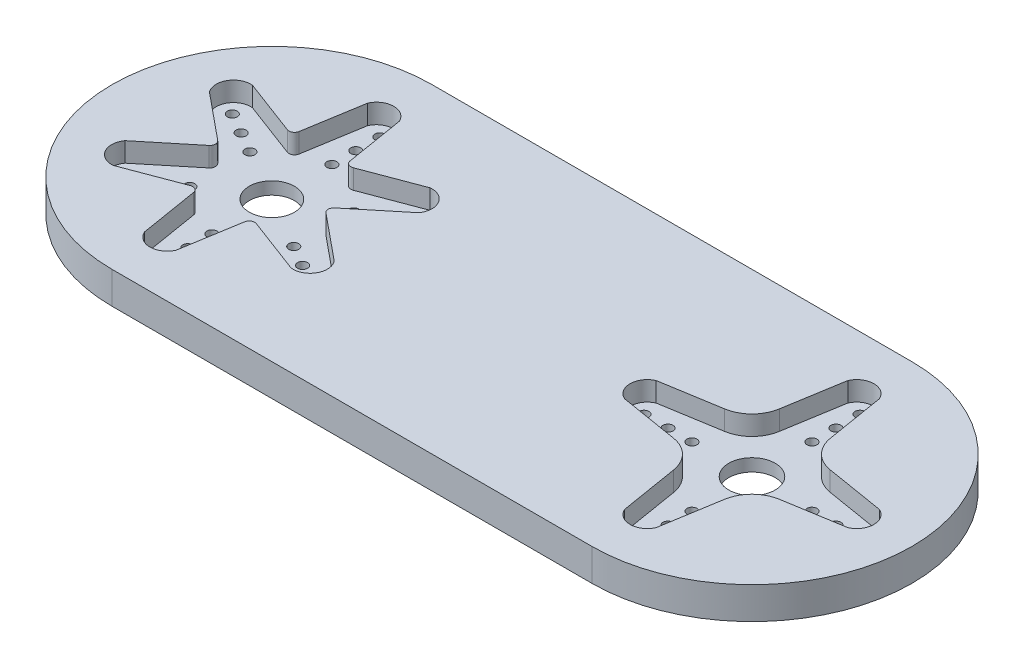
SolidWorks part; units mm, degrees
material "PLA"
ref_plane "Front Plane" through (0, 0, 0) normal (0, 0, 1) x (1, 0, 0)
ref_plane "Top Plane" through (0, 0, 0) normal (0, 1, 0) x (1, 0, 0)
ref_plane "Right Plane" through (0, 0, 0) normal (1, 0, 0) x (0, 0, -1)
sketch "Sketch1" plane through (0, 0, 0) normal (0, 1, 0) x (1, 0, 0)
  line L0 (-30, 0) -> (30, 0) construction
  line L1 (-30, 20) -> (30, 20)
  line L2 (-30, -20) -> (30, -20)
  arc A0 (-30, 20) -> (-30, -20) centre (-30, 0) ccw
  arc A1 (30, -20) -> (30, 20) centre (30, 0) ccw
  point P2 (0, 0)
  dimension "D1" = 60
  dimension "D2" = 40
extrude "Boss-Extrude1" add sketch "Sketch1" along normal blind 4
sketch "Sketch2" plane through (0, 4, 0) normal (0, 1, 0) x (1, 0, 0)
  line L0 (-30.0441, 0.0218) -> (-30.0441, -7.4787) construction
  line L1 (-30.0441, 0.0218) -> (-26.8597, 6.6199) construction
  line L2 (-30.0441, 0.0218) -> (-25.9221, 6.0786) construction
  line L3 (-30.0441, 0.0218) -> (-30.0441, 15.2618) construction
  line L4 (-30.0441, -7.4787) -> (-30.0441, -10.4787) construction
  line L5 (-30.0441, -10.4787) -> (-30.0441, -13.4787) construction
  line L18 (-30, 20) -> (-30, -20) construction
  line L19 (30, 20) -> (-30, 20) construction
  line L20 (-26.8597, 6.6199) -> (-28.0706, 13.9723)
  line L21 (-33.2284, 6.6199) -> (-32.0175, 13.9723)
  line L22 (-25.9221, 6.0786) -> (-18.9493, 8.706)
  line L23 (-22.7377, 0.5631) -> (-16.9759, 5.288)
  line L24 (-22.7377, -0.5195) -> (-16.9759, -5.2445)
  line L25 (-25.9221, -6.035) -> (-18.9493, -8.6625)
  line L26 (-26.8597, -6.5763) -> (-28.0706, -13.9287)
  line L27 (-33.2284, -6.5763) -> (-32.0175, -13.9287)
  line L28 (-34.166, -6.035) -> (-41.1388, -8.6625)
  line L29 (-37.3504, -0.5195) -> (-43.1122, -5.2445)
  line L30 (-37.3504, 0.5631) -> (-43.1122, 5.288)
  line L31 (-34.166, 6.0786) -> (-41.1388, 8.706)
  line L32 (30, 20) -> (30, -20) construction
  line L33 (30, 0) -> (30, -7.5005) construction
  line L34 (36.5981, -3.1844) -> (43.9505, -1.9734)
  line L35 (36.5981, 3.1844) -> (43.9505, 1.9734)
  line L36 (30, 0) -> (33.1844, 6.5981) construction
  line L37 (30, 0) -> (34.1219, 6.0568) construction
  line L38 (30, 0) -> (30, 15.24) construction
  line L39 (30, -7.5005) -> (30, -10.5005) construction
  line L40 (30, -10.5005) -> (30, -13.5005) construction
  line L41 (26.8156, -6.5981) -> (28.0266, -13.9505)
  line L42 (33.1844, -6.5981) -> (31.9734, -13.9505)
  line L43 (23.4019, 3.1844) -> (16.0495, 1.9734)
  line L44 (23.4019, -3.1844) -> (16.0495, -1.9734)
  line L45 (33.1844, 6.5981) -> (31.9734, 13.9505)
  line L46 (26.8156, 6.5981) -> (28.0266, 13.9505)
  line L47 (33.1844, -6.5981) -> (31.9734, -13.9505)
  line L48 (26.8156, -6.5981) -> (28.0266, -13.9505)
  arc A29 (-30, 20) -> (-30, -20) centre (-30, 0) ccw construction
  arc A30 (-32.0175, 13.9723) -> (-28.0706, 13.9723) centre (-30.0441, 13.107) cw
  arc A31 (-18.9493, 8.706) -> (-16.9759, 5.288) centre (-18.7119, 6.5644) cw
  arc A32 (-16.9759, -5.2445) -> (-18.9493, -8.6625) centre (-18.7119, -6.5208) cw
  arc A33 (-28.0706, -13.9287) -> (-32.0175, -13.9287) centre (-30.0441, -13.0635) cw
  arc A34 (-41.1388, -8.6625) -> (-43.1122, -5.2445) centre (-41.3762, -6.5208) cw
  arc A35 (-43.1122, 5.288) -> (-41.1388, 8.706) centre (-41.3762, 6.5644) cw
  arc A36 (-26.8597, 6.6199) -> (-25.9221, 6.0786) centre (-26.169, 6.7336) ccw
  arc A37 (-22.7377, 0.5631) -> (-22.7377, -0.5195) centre (-22.2939, 0.0218) ccw
  arc A38 (-25.9221, -6.035) -> (-26.8597, -6.5763) centre (-26.169, -6.6901) ccw
  arc A39 (-33.2284, -6.5763) -> (-34.166, -6.035) centre (-33.9191, -6.6901) ccw
  arc A40 (-37.3504, -0.5195) -> (-37.3504, 0.5631) centre (-37.7942, 0.0218) ccw
  arc A41 (-34.166, 6.0786) -> (-33.2284, 6.6199) centre (-33.9191, 6.7336) ccw
  circle A42 centre (-30.0441, -7.4787) radius 0.625
  circle A43 centre (-30.0441, -10.4787) radius 0.625
  circle A44 centre (-41.7358, -6.7285) radius 0.625
  circle A45 centre (-39.1377, -5.2285) radius 0.625
  circle A46 centre (-36.5396, -3.7285) radius 0.625
  circle A47 centre (-41.7358, 6.772) radius 0.625
  circle A48 centre (-39.1377, 5.272) radius 0.625
  circle A49 centre (-36.5396, 3.772) radius 0.625
  circle A50 centre (-30.0441, 13.5222) radius 0.625
  circle A51 centre (-30.0441, 10.5222) radius 0.625
  circle A52 centre (-30.0441, 7.5222) radius 0.625
  circle A53 centre (-18.3523, 6.772) radius 0.625
  circle A54 centre (-20.9504, 5.272) radius 0.625
  circle A55 centre (-23.5485, 3.772) radius 0.625
  circle A56 centre (-18.3523, -6.7285) radius 0.625
  circle A57 centre (-20.9504, -5.2285) radius 0.625
  circle A58 centre (-23.5485, -3.7285) radius 0.625
  arc A59 (30, -20) -> (30, 20) centre (30, 0) ccw construction
  arc A60 (28.0266, 13.9505) -> (31.9734, 13.9505) centre (30, 13.0852) cw
  arc A61 (31.9734, -13.9505) -> (28.0266, -13.9505) centre (30, -13.0852) cw
  circle A62 centre (30, -7.5005) radius 0.625
  circle A63 centre (30, -10.5005) radius 0.625
  circle A64 centre (30, -13.5005) radius 0.625
  circle A65 centre (30, 13.5005) radius 0.625
  circle A66 centre (30, 10.5005) radius 0.625
  circle A67 centre (30, 7.5005) radius 0.625
  circle A68 centre (40.5005, 0) radius 0.625
  circle A69 centre (37.5005, 0) radius 0.625
  circle A70 centre (43.5005, 0) radius 0.625
  arc A71 (43.9505, 1.9734) -> (43.9505, -1.9734) centre (43.0852, 0) cw
  circle A72 centre (30, -10.5005) radius 0.625
  circle A73 centre (30, -7.5005) radius 0.625
  circle A74 centre (30, -13.5005) radius 0.625
  arc A75 (31.9734, -13.9505) -> (28.0266, -13.9505) centre (30, -13.0852) cw
  circle A76 centre (19.4995, 0) radius 0.625
  circle A77 centre (22.4995, 0) radius 0.625
  circle A78 centre (16.4995, 0) radius 0.625
  arc A79 (16.0495, -1.9734) -> (16.0495, 1.9734) centre (16.9148, 0) cw
  arc A80 (33.1844, 6.5981) -> (36.5981, 3.1844) centre (37.2712, 7.2712) ccw
  arc A81 (36.5981, -3.1844) -> (33.1844, -6.5981) centre (37.2712, -7.2712) ccw
  arc A82 (26.8156, -6.5981) -> (23.4019, -3.1844) centre (22.7288, -7.2712) ccw
  arc A83 (23.4019, 3.1844) -> (26.8156, 6.5981) centre (22.7288, 7.2712) ccw
  point P4 (-30.0441, 0.0218)
  point P9 (-30.0441, 0.0218)
  point P12 (-30.0436, 0.0226)
  point P15 (-30.0426, 0.0226)
  point P19 (-30.0421, 0.0218)
  point P23 (-30.0426, 0.0209)
  point P27 (-30.0436, 0.0209)
  point P30 (-30.0431, 0.0218)
  point P53 (-30.0441, 0.0218)
  point P70 (-30.0441, 0.0218)
  point P77 (-30.0441, 0.0218)
  point P84 (-30.0441, 0.0218)
  point P103 (30, 0)
  point P110 (30, 0)
  point P175 (30, 7.5005)
  point P176 (30, 0)
  point P177 (30, 10.5005)
  point P178 (30, 13.5005)
  dimension "D1" = 7.3263
  dimension "D2" = 8.474
  dimension "D3" = 7.4515
  dimension "D4" = 144.884
  dimension "D5" = 3
  dimension "D6" = 3
  dimension "D7" = 7.5005
  dimension "D8" = 7.3263
  dimension "D9" = 7.4515
  dimension "D10" = 3
extrude "Cut-Extrude1" cut sketch "Sketch2" against normal blind 2.44 contours A83 L43 A79 L44 A82 L41 A61 L42 A81 L34 A71 L35 A80 L45 A60 L46 A78 A77 A76 A70 A69 A68 A67 A66 A65 A64 A63 A62 | L20 A30 L21 A41 L31 A35 L30 A40 L29 A34 L28 A39 L27 A33 L26 A38 L25 A32 L24 A37 L23 A31 L22 A36 region at (30, 4, 0)
sketch "Sketch3" plane through (0, 1.56, 0) normal (0, 1, 0) x (1, 0, 0)
  circle A3 centre (-30.0441, 13.5222) radius 0.625
  circle A4 centre (-30.0441, 10.5222) radius 0.625
  circle A5 centre (-30.0441, 7.5222) radius 0.625
  circle A21 centre (-23.5485, 3.772) radius 0.625
  circle A22 centre (-20.9504, 5.272) radius 0.625
  circle A23 centre (-18.3523, 6.772) radius 0.625
  circle A24 centre (-23.5485, -3.7285) radius 0.625
  circle A25 centre (-20.9504, -5.2285) radius 0.625
  circle A26 centre (-18.3523, -6.7285) radius 0.625
  circle A27 centre (-30.0441, -7.4787) radius 0.625
  circle A28 centre (-30.0441, -10.4787) radius 0.625
  circle A29 centre (-30.0441, -13.4787) radius 0.625
  circle A30 centre (-36.5396, -3.7285) radius 0.625
  circle A31 centre (-39.1377, -5.2285) radius 0.625
  circle A32 centre (-41.7358, -6.7285) radius 0.625
  circle A33 centre (-36.5396, 3.772) radius 0.625
  circle A34 centre (-39.1377, 5.272) radius 0.625
  circle A35 centre (-41.7358, 6.772) radius 0.625
  circle A36 centre (-30.0441, 0.0218) radius 2.82
  circle A54 centre (30, 0) radius 2.9
  circle A55 centre (30, 7.5005) radius 0.625
  circle A56 centre (30, 10.5005) radius 0.625
  circle A57 centre (30, 13.5005) radius 0.625
  circle A58 centre (16.4995, 0) radius 0.625
  circle A59 centre (19.4995, 0) radius 0.625
  circle A60 centre (22.4995, 0) radius 0.625
  circle A61 centre (30, -13.5005) radius 0.625
  circle A62 centre (30, -10.5005) radius 0.625
  circle A63 centre (30, -7.5005) radius 0.625
  circle A64 centre (43.5005, 0) radius 0.625
  circle A65 centre (40.5005, 0) radius 0.625
  circle A66 centre (37.5005, 0) radius 0.625
  point P9 (-30.0441, 0.0218)
  point P43 (-30.0441, 0.0218)
  point P55 (30, 0)
  point P77 (30, 0)
extrude "Cut-Extrude3" cut sketch "Sketch3" against normal through all both and the other way through all contours A36 | A24 | A25 | A26 | A22 | A5 | A34 | A35 | A33 | A3 | A31 | A27 | A54 | A61 | A64 | A65 | A56 | A57 | A55 | A60 | A59 | A58 | A23 | A21 | A4 | A30 | A32 | A28 | A29 | A62 | A63 | A66 region at (-30.0441, 1.56, -13.5222) region at (-30.0441, 1.56, -7.5222) region at (-20.9504, 1.56, -5.272) region at (-23.5485, 1.56, 3.7285) region at (-20.9504, 1.56, 5.2285) region at (-18.3523, 1.56, 6.7285) region at (-30.0441, 1.56, 7.4787) region at (-39.1377, 1.56, 5.2285) region at (-36.5396, 1.56, -3.772) region at (-39.1377, 1.56, -5.272) region at (-41.7358, 1.56, -6.772) region at (-30.0441, 1.56, -0.0218) region at (30, 1.56, 0) region at (30, 1.56, -7.5005) region at (30, 1.56, -10.5005) region at (30, 1.56, -13.5005) region at (16.4995, 1.56, 0) region at (19.4995, 1.56, 0) region at (22.4995, 1.56, 0) region at (30, 1.56, 13.5005) region at (43.5005, 1.56, 0) region at (40.5005, 1.56, 0)
